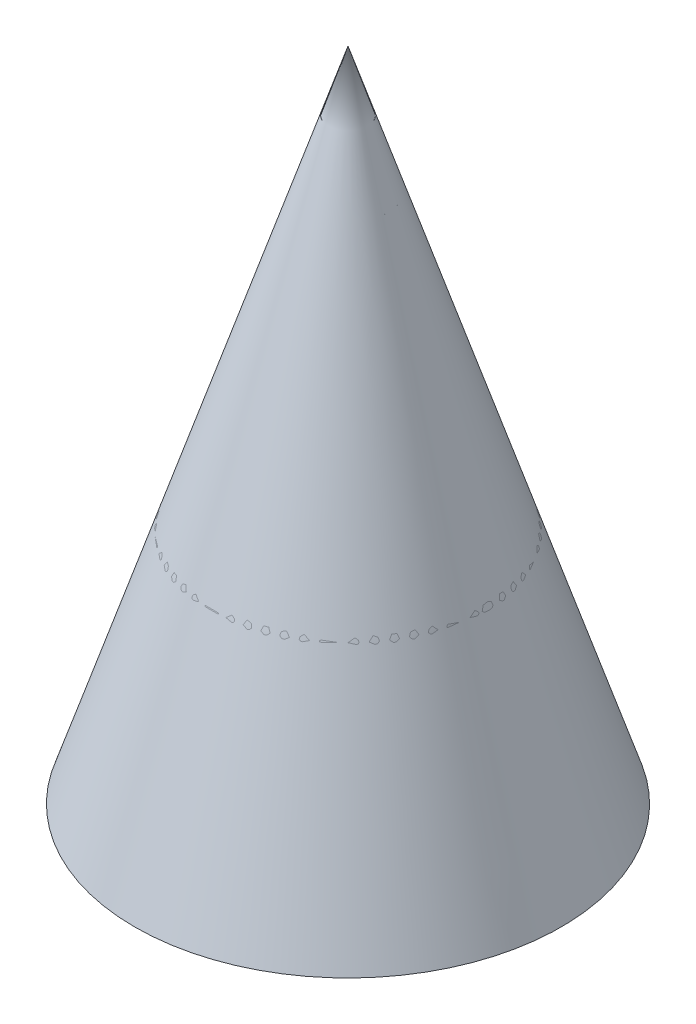
SolidWorks part; units mm, degrees
ref_plane "前视基准面" through (0, 0, 0) normal (0, 0, 1) x (1, 0, 0)
ref_plane "上视基准面" through (0, 0, 0) normal (0, 1, 0) x (1, 0, 0)
ref_plane "右视基准面" through (0, 0, 0) normal (1, 0, 0) x (0, 0, -1)
sketch "草图1" plane through (0, 0, 0) normal (0, 0, 1) x (1, 0, 0)
  line L0 (0, 0) -> (0, 230)
  line L1 (0, 230) -> (74.7315, 0)
  line L2 (74.7315, 0) -> (0, 0)
  line L3 (0, 118.336) -> (0, -13.1932) construction
  dimension "D1" = 18
  dimension "D2" = 230
revolve "旋转1" add sketch "草图1" angle 360 about L3
sketch "草图2" plane through (0, 0, 0) normal (0, 0, 1) x (1, 0, 0)
  line L1 (0, 230) -> (0, -25.6589) construction
  line L2 (0, 196.454) -> (0, 166.464)
  line L3 (0, 118.1916) -> (0, 18.2016)
  arc A0 (0, 166.464) -> (0, 196.454) centre (0, 181.459) ccw
  arc A1 (0, 18.2016) -> (0, 118.1916) centre (0, 68.1966) ccw
  dimension "D1" = 29.99
  dimension "D2" = 99.99
  dimension "D3" = 48.541
  dimension "D4" = 161.8034
revolve "切除-旋转1" cut sketch "草图2" angle 360 about L1
